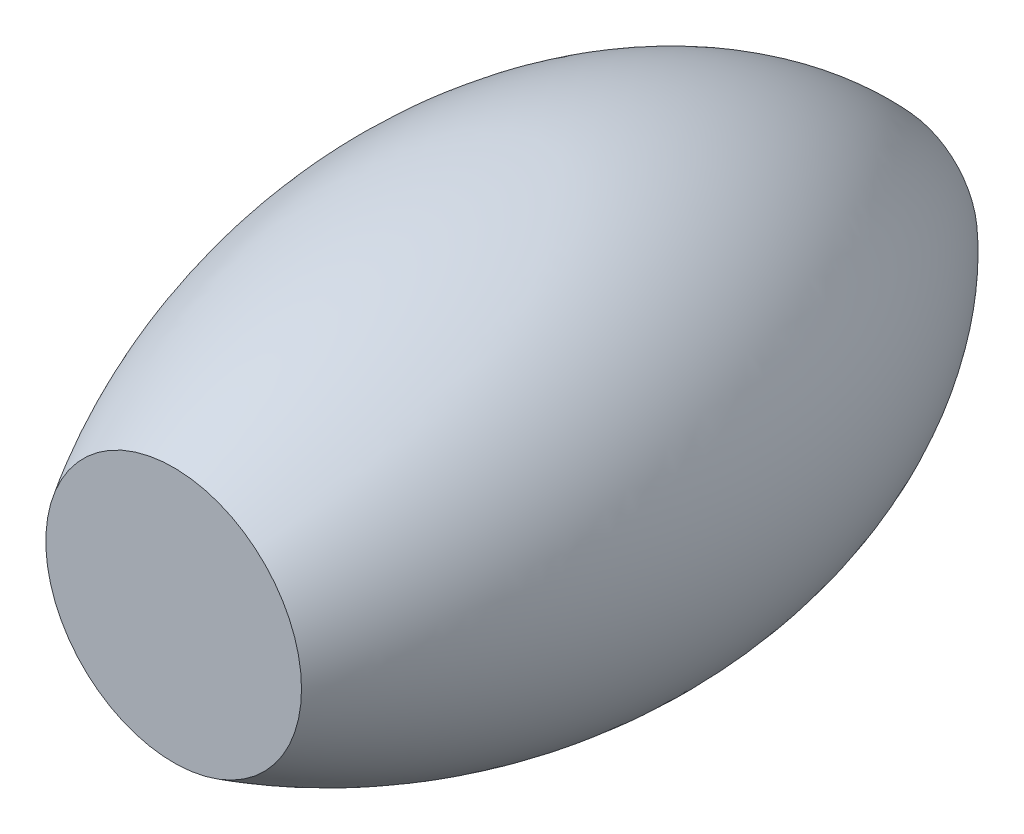
SolidWorks part; units mm, degrees
material "AISI 304"
ref_plane "Frontal" through (0, 0, 0) normal (0, 0, 1) x (1, 0, 0)
ref_plane "Superior" through (0, 0, 0) normal (0, 1, 0) x (1, 0, 0)
ref_plane "Derecha" through (0, 0, 0) normal (1, 0, 0) x (0, 0, -1)
ref_plane "Plano1" through (0, 0, 0) normal (0, 0, 1) x (1, 0, 0)
sketch "Croquis1" plane through (0, 0, 0) normal (0, 0, 1) x (1, 0, 0)
  circle A0 centre (0, 0) radius 65
  dimension "D1" = 130
ref_axis "Eje1" through (0, 0, -88.99) along (0, 0, 1)
sketch "Croquis3" plane through (0, 0, 0) normal (0, 1, 0) x (1, 0, 0)
  line L0 (0, -100) -> (0, 100) construction
  line L1 (0, -100) -> (-35, -100)
  line L2 (0, -55) -> (-55, -55) construction
  line L3 (0, 45) -> (-55, 45) construction
  line L4 (0, 100) -> (-20, 100)
  line L5 (0, 0) -> (-62.5, 0) construction
  line L6 (0, -100) -> (0, 100)
  line L7 (0, 100) -> (0, -100)
  spline S0 degree 3 poles (-20, 100) (-48.56, 74.1003) (-74.0191, 2.1093) (-53.1787, -70.2059) (-35, -100) knots 0 0 0 0 0.514055 1 1 1 1
  dimension "D1" = 200
  dimension "D2" = 45
  dimension "D3" = 55
  dimension "D4" = 55
  dimension "D5" = 62.5
  dimension "D6" = 35
  dimension "D7" = 20
  dimension "D8" = 55
revolve "Revolución1" add sketch "Croquis3" angle 360 about L6 region at (-26.9084, 0, 3.1958)
